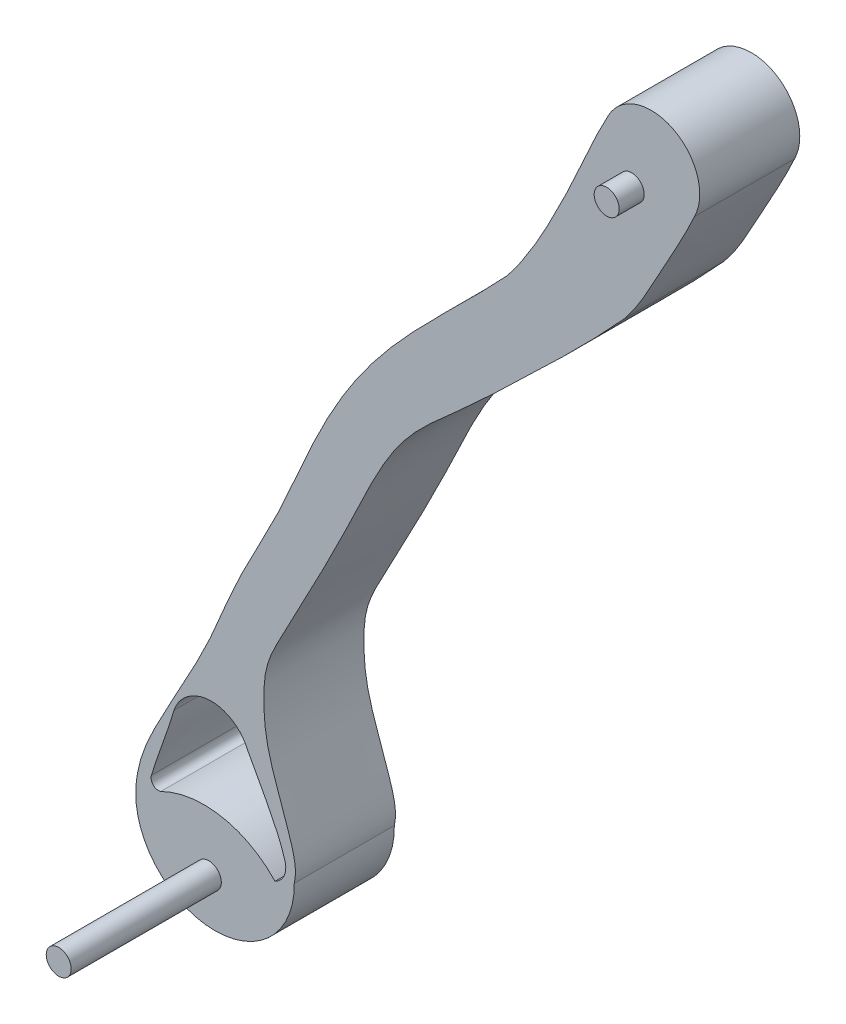
SolidWorks part; units mm, degrees
ref_plane "Front Plane" through (0, 0, 0) normal (0, 0, 1) x (1, 0, 0)
ref_plane "Top Plane" through (0, 0, 0) normal (0, 1, 0) x (1, 0, 0)
ref_plane "Right Plane" through (0, 0, 0) normal (1, 0, 0) x (0, 0, -1)
sketch "Sketch1" plane through (0, 0, 0) normal (0, 0, 1) x (1, 0, 0)
  line L0 (-958.0425, 331.2451) -> (-108.0425, 331.2451) construction
  line L1 (-128.5107, -145.2932) -> (-128.3596, -136.483) construction
  arc A0 (-128.4353, -140.8969) -> (-65.075, -140.8969) centre (-96.7551, -141.4405) ccw
  arc A1 (94.8965, 169.931) -> (60.3872, 187.5427) centre (77.6418, 178.7368) ccw
  spline S0 degree 3 poles (19.939, 111.9522) (3.6523, 94.329) (-20.2496, 73.6219) (-45.6524, 39.0411) (-58.8426, 13.6097) (-71.7895, -18.072) (-87.7389, -45.5003) (-100.8634, -79.9214) (-115.4521, -103.7884) (-126.1439, -125.77) (-128.3402, -135.3537) (-128.4353, -140.8969) knots 0 0 0 0 0.227861 0.297083 0.405626 0.498416 0.621398 0.705378 0.846798 0.885361 0.937345 0.937345 0.937345 0.937345
  spline S1 degree 3 poles (-65.075, -140.8969) (-63.9077, -135.8746) (-66.351, -126.6592) (-71.6977, -112.1281) (-76.3347, -98.4722) (-77.5417, -84.2072) (-76.962, -70.3421) (-68.8858, -55.695) (-58.2138, -35.3055) (-45.1098, -10.2853) (-33.8512, 14.9393) (-19.4413, 38.7618) (0.3461, 54.8463) (30.1497, 83.3531) (52.0053, 104.156) (66.8759, 120.5503) knots 0 0 0 0 0.04687 0.090142 0.148581 0.183457 0.2269 0.278591 0.340349 0.448131 0.547902 0.604794 0.712231 0.788345 1 1 1 1
  spline S2 degree 3 poles (66.8759, 120.5503) (72.3866, 127.1991) (81.1017, 144.0708) (90.5876, 160.476) (94.8965, 169.931) knots 0 0 0 0 0.452322 1 1 1 1
  spline S3 degree 3 poles (19.939, 111.9522) (26.2481, 119.8006) (36.0718, 136.3931) (48.5414, 162.1802) (55.829, 179.3017) (60.3872, 187.5427) knots 0 0 0 0 0.350646 0.671543 1 1 1 1
extrude "Boss-Extrude1" add sketch "Sketch1" along normal blind 40
sketch "Sketch2" plane through (0, 0, 0) normal (0, 0, -1) x (-1, 0, 0)
  arc A2 (68.7561, -135.1012) -> (72.7672, -144.0007) centre (76.035, -137.1742) ccw
  arc A3 (118.4099, -135.7129) -> (72.7672, -144.0007) centre (101.1511, -170.4908) ccw
  arc A4 (118.4099, -135.7129) -> (122.1174, -131.9212) centre (119.3954, -132.9681) ccw
  arc A5 (113.1744, -105.0297) -> (83.7676, -103.9711) centre (98.268, -110.1391) ccw
  spline S0 degree 3 poles (83.7676, -103.9711) (83.5874, -104.2987) (81.914, -107.3391) (79.5057, -111.7138) (76.6248, -117.1039) (74.515, -121.1655) (72.5234, -125.1819) (70.7511, -129.1745) (69.5362, -132.4779) (68.9336, -134.4701) (68.7561, -135.1012) knots 0.787262 0.787262 0.787262 0.787262 0.7908 0.820109 0.834763 0.849418 0.864072 0.878727 0.893381 0.900143 0.900143 0.900143 0.900143
  spline S1 degree 3 poles (122.1174, -131.9212) (121.9022, -131.1213) (121.4408, -129.5703) (120.6719, -127.1927) (119.6526, -124.1703) (118.3047, -120.3638) (116.0834, -114.194) (114.3135, -109.0461) (113.272, -105.3807) (113.1744, -105.0297) knots 0.0362 0.0362 0.0362 0.0362 0.044998 0.052823 0.060648 0.076298 0.091948 0.123247 0.12655 0.12655 0.12655 0.12655
sketch "Sketch3" plane through (0, 0, 40) normal (0, 0, 1) x (1, 0, 0)
  circle A1 centre (69.8194, 167.583) radius 5
extrude "Boss-Extrude3" add sketch "Sketch3" along normal blind 10
extrude "Cut-Extrude1" cut sketch "Sketch2" against normal blind 40
extrude "Boss-Extrude6" add sketch "Sketch3<2>" against normal blind 50
sketch "Sketch3<2>" plane through (0, 0, 40) normal (0, 0, 1) x (1, 0, 0) same geometry as "Sketch3"
sketch "Sketch4" plane through (0, 0, 40) normal (0, 0, 1) x (1, 0, 0)
  circle A0 centre (-99.2301, -155.1295) radius 5
  arc A3 (-122.1174, -131.9212) -> (-118.4099, -135.7129) centre (-119.3954, -132.9681) ccw construction
  point P2 (0, 0)
  point P9 (0, 0)
  point P13 (-121.4806, -135.007)
  dimension "D1" = 10
  dimension "D2" = 30
extrude "Boss-Extrude7" add sketch "Sketch4" along normal blind 60
